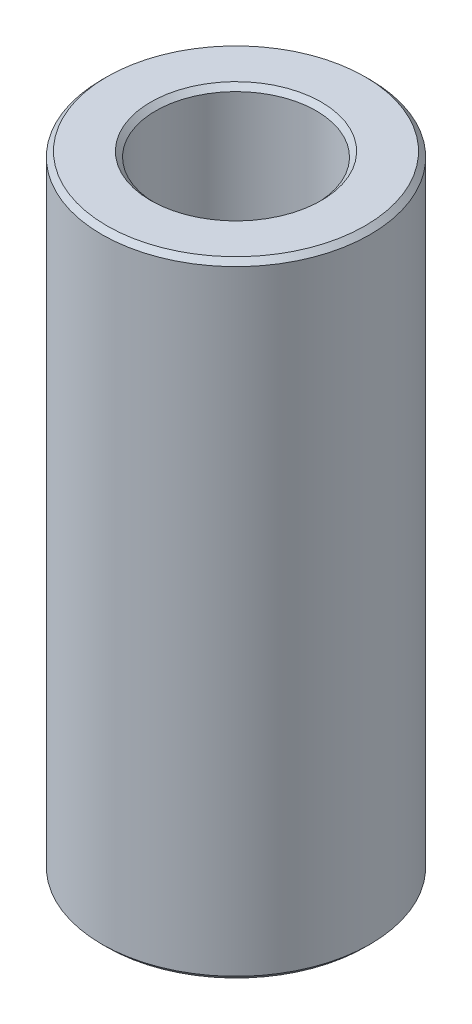
SolidWorks part; units mm, degrees
ref_plane "Front Plane" through (0, 0, 0) normal (0, 0, 1) x (1, 0, 0)
ref_plane "Top Plane" through (0, 0, 0) normal (0, 1, 0) x (1, 0, 0)
ref_plane "Right Plane" through (0, 0, 0) normal (1, 0, 0) x (0, 0, -1)
sketch "Sketch1" plane through (0, 0, 0) normal (0, 1, 0) x (1, 0, 0)
  circle A0 centre (0, 0) radius 47.5
  dimension "SLEEVE_OD" = 95
extrude "Boss-Extrude1" add sketch "Sketch1" along normal blind 221.2036
sketch "Sketch2" plane through (0, 0, 0) normal (0, 1, 0) x (1, 0, 0)
  circle A0 centre (0, 0) radius 28.4231
  dimension "BORE_D" = 56.8462
extrude "Cut-Extrude1" cut sketch "Sketch2" along normal through all
chamfer "Chamfer1" distance 1.7891 angle 45 4 edges at (0, 221.2036, 28.4231) (0, 0, 28.4231) (0, 0, 47.5) (0, 221.2036, 47.5)
